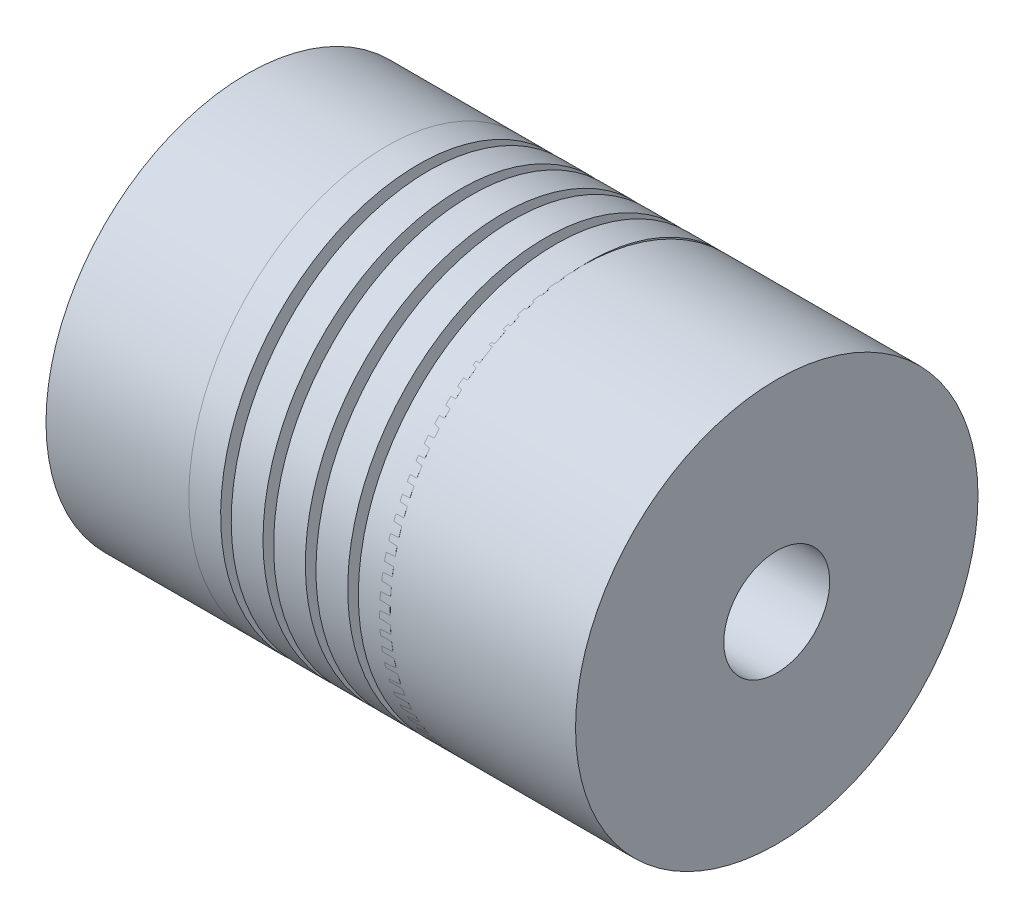
SolidWorks part; units mm, degrees
other "Marcação1"
sketch "Esboço5" plane through (-0.021, -9.9931, -9.5042) normal (-0.0499, -0.5929, -0.8037) x (-0.9894, 0.1393, -0.0413)
sketch "Esboço12" plane through (-7.5, -9.9889, -9.5) normal (-0.0499, -0.5929, -0.8037) x (-0.9894, 0.1393, -0.0413)
sketch "Esboço13" plane through (-7.5, -9.9889, -9.5) normal (-0.0499, -0.5929, -0.8037) x (-0.9894, 0.1393, -0.0413)
ref_plane "Plano frontal" through (0, 0, 0) normal (0, 0, 1) x (1, 0, 0)
ref_plane "Plano superior" through (0, 0, 0) normal (0, 1, 0) x (1, 0, 0)
ref_plane "Plano direito" through (0, 0, 0) normal (1, 0, 0) x (0, 0, -1)
sketch "Esboço1" plane through (0, 0, 0) normal (0, 0, 1) x (1, 0, 0)
  line L0 (0, 0) -> (0, 2.5)
  line L1 (0, 2.5) -> (25, 2.5)
  line L2 (0, 0) -> (25, 0)
  line L3 (25, 0) -> (25, 2.5)
  line L4 (0, 2.5) -> (0, 9.5)
  line L5 (0, 9.5) -> (2, 9.5)
  line L6 (2, 9.5) -> (2, 2.5)
revolve "Revolução1" add sketch "Esboço1" angle 360 about L2
sketch "Esboço3" plane through (0, 0, 0) normal (-1, 0, 0) x (0, 0, 1)
  circle A0 centre (0, 0) radius 2.5
  dimension "D1" = 5
curve "Hélice/Espiral1" pitch 2 height 10 turns 5
sketch "Esboço4" plane through (0, 0, 0) normal (0, 1, 0) x (1, 0, 0)
  line L9 (0.25, 9.5) -> (1.75, 9.5)
  line L11 (1.75, 9.5) -> (1.75, 2.5)
  line L12 (25, 2.5) -> (0, 2.5) construction
  line L13 (1.75, 2.5) -> (0.25, 2.5)
  line L14 (0.25, 2.5) -> (0.25, 9.5)
sweep "Varredura1" add profiles "Esboço4" path "Hélice/Espiral1"
ref_plane "Plano1" through (-7.5, 0, 0) normal (-1, 0, 0) x (0, 0, 1)
sketch "Esboço7" plane through (-7.5, 0, 0) normal (-1, 0, 0) x (0, 0, 1)
  circle A0 centre (0, 0) radius 9.5
  dimension "D1" = 19
extrude "Ressalto-extrusão3" add sketch "Esboço7" against normal blind 7.25
ref_plane "Plano2" through (17.5, 0, 0) normal (-1, 0, 0) x (0, 0, 1)
sketch "Esboço9" plane through (-7.5, 0, 0) normal (-1, 0, 0) x (0, 0, 1)
  circle A0 centre (0, 0) radius 2.5
sketch "Esboço10" plane through (17.5, 0, 0) normal (-1, 0, 0) x (0, 0, 1)
  circle A0 centre (0, 0) radius 9.5
extrude "Ressalto-extrusão5" add sketch "Esboço10" along normal blind 9.25 separate body
sketch "Esboço11" plane through (-7.5, 0, 0) normal (-1, 0, 0) x (0, 0, 1)
  circle A0 centre (0, 0) radius 2.5
extrude "Corte-extrusão2" cut sketch "Esboço11" against normal up to surface (32.5 mm away) up to face at (25, 0, 2.5)
